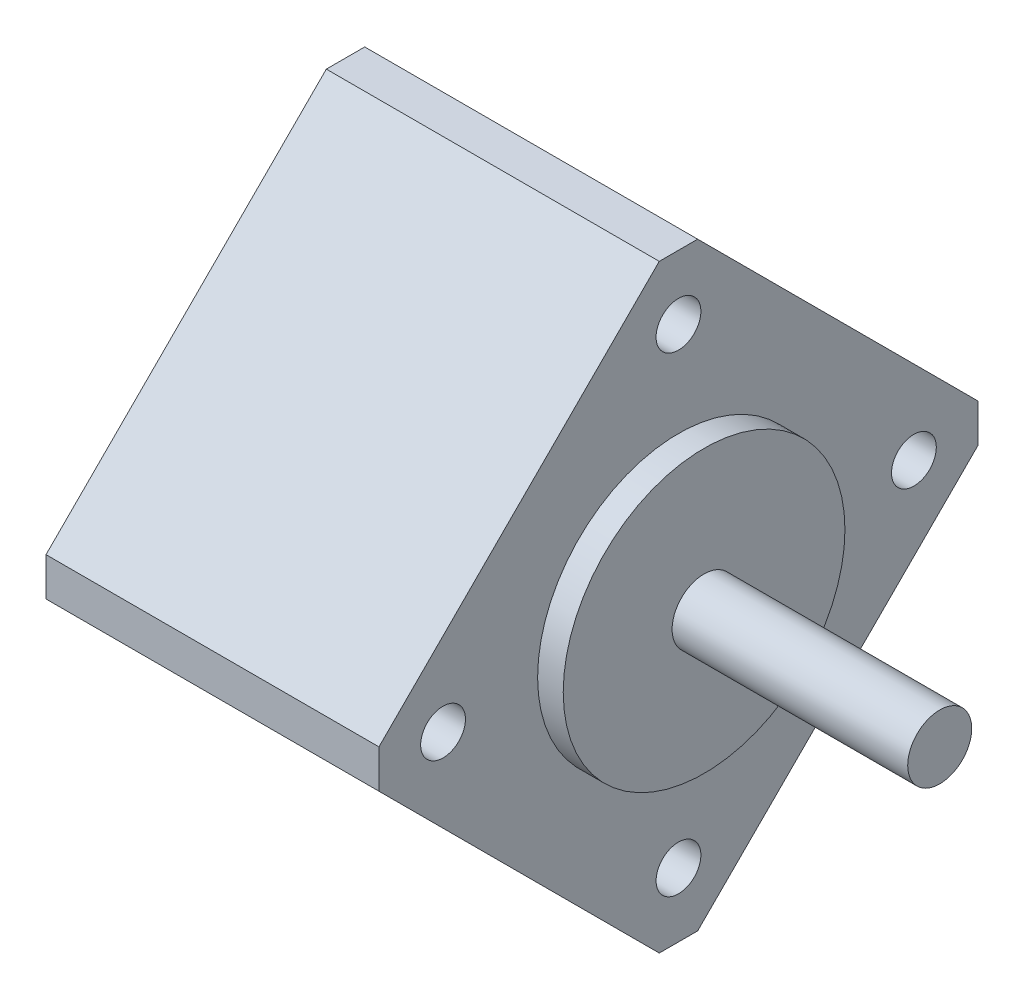
SolidWorks part; units mm, degrees
ref_plane "Front Plane" through (0, 0, 0) normal (0, 0, 1) x (1, 0, 0)
ref_plane "Top Plane" through (0, 0, 0) normal (0, 1, 0) x (1, 0, 0)
ref_plane "Right Plane" through (0, 0, 0) normal (1, 0, 0) x (0, 0, -1)
sketch "Sketch1" plane through (0, 0, 0) normal (0, 0, 1) x (1, 0, 0)
  line L0 (0, 0) -> (58.591, 0) construction
  line L2 (0, 0) -> (18.4, 0)
  line L3 (0, 0) -> (0, 2.5)
  line L4 (0, 2.5) -> (18.4, 2.5)
  line L5 (18.4, 0) -> (18.4, 2.5)
  line L6 (6.0094, 2.5) -> (6.0094, 6)
  line L11 (6.0094, 6) -> (9.9794, 6)
  line L16 (12.9794, 6) -> (12.9794, 3)
  line L17 (12.9794, 3) -> (13.6398, 3)
  line L18 (13.6398, 3) -> (13.6398, 2.5)
  line L19 (13.6398, 2.5) -> (6.0094, 2.5)
  line L22 (13.6398, 2.5) -> (16.1198, 2.5)
  line L23 (13.6398, 2.5) -> (13.6398, 4)
  line L24 (13.6398, 4) -> (16.1198, 4)
  line L25 (16.1198, 2.5) -> (16.1198, 4)
  line L27 (6.0094, 6) -> (9.9794, 6)
  line L28 (6.0094, 6) -> (6.0094, 9)
  line L29 (6.0094, 9) -> (9.9794, 9)
  line L30 (9.9794, 6) -> (9.9794, 9)
  line L31 (6.0094, 9) -> (6.0094, 8.25)
  line L32 (6.0094, 8.25) -> (5.0094, 8.25)
  line L33 (8.6609, 22.001) -> (8.6609, 12.476) construction
  line L34 (5.0094, 12.476) -> (12.3124, 12.476)
  line L35 (9.9794, 9) -> (12.3124, 9)
  line L36 (5.0094, 7.9375) -> (1.8344, 7.9375)
  line L37 (5.0094, 8.25) -> (5.0094, 12.476)
  line L38 (5.0094, 7.9375) -> (5.0094, 13.9365)
  line L39 (5.0094, 13.9365) -> (1.8344, 13.9365)
  line L40 (1.8344, 7.9375) -> (1.8344, 13.9365)
  line L41 (5.0094, 22.001) -> (12.3124, 22.001)
  line L42 (5.0094, 22.001) -> (5.0094, 30.1625)
  line L43 (5.0094, 30.1625) -> (12.3124, 30.1625)
  line L44 (12.3124, 22.001) -> (12.3124, 30.1625)
  line L49 (16.6398, 22.001) -> (16.6398, 7.5)
  line L51 (23.0198, 7.5) -> (23.0198, 6.5)
  line L54 (16.1198, 4) -> (13.6398, 4)
  line L56 (18.0398, 7.5) -> (23.0198, 7.5)
  line L57 (13.3124, 22.001) -> (16.6398, 22.001)
  line L58 (16.1198, 3.5) -> (20.0198, 3.5)
  line L59 (29.9098, 14) -> (26.9098, 11)
  line L60 (4.0094, 31.75) -> (18.0398, 31.75)
  line L61 (18.0398, 7.5) -> (23.0198, 7.5)
  line L62 (18.0398, 7.5) -> (18.0398, 12)
  line L63 (18.0398, 12) -> (23.0198, 12)
  line L64 (23.0198, 7.5) -> (23.0198, 12)
  line L65 (18.0398, 31.75) -> (18.0398, 12)
  line L66 (23.0198, 11) -> (26.9098, 11)
  line L67 (34.8098, 23) -> (31.3098, 19.5)
  line L68 (35.8098, 31) -> (38.7998, 33.99)
  line L69 (29.9098, 14) -> (29.9098, 15)
  line L70 (29.9098, 15) -> (22.9398, 15)
  line L71 (22.9398, 15) -> (21.0398, 15)
  line L72 (18.0398, 7.5) -> (16.6398, 7.5)
  line L73 (21.0398, 15) -> (21.0398, 43)
  line L74 (19.5798, 40) -> (9.6198, 40)
  line L75 (9.6198, 40) -> (4.0094, 40)
  line L76 (21.0398, 43) -> (19.5798, 43)
  line L77 (22.9398, 15) -> (29.9098, 15)
  line L78 (22.9398, 15) -> (22.9398, 21)
  line L79 (22.9398, 21) -> (29.9098, 21)
  line L80 (29.9098, 15) -> (29.9098, 21)
  line L81 (9.6198, 40) -> (19.5798, 40)
  line L82 (9.6198, 40) -> (9.6198, 50)
  line L83 (9.6198, 50) -> (19.5798, 50)
  line L84 (19.5798, 40) -> (19.5798, 50)
  line L85 (4.0094, 40) -> (4.0094, 31.75)
  line L86 (12.9794, 3) -> (12.9794, 2.5)
  line L87 (31.3098, 19.5) -> (29.9098, 19.5)
  line L88 (21.4694, 63.5) -> (21.4694, 51.308)
  line L89 (21.4694, 63.5) -> (25.9398, 63.5)
  line L90 (25.9398, 63.5) -> (25.9398, 25)
  line L91 (27.8398, 25) -> (25.9398, 25)
  line L92 (9.6198, 48) -> (8.1598, 48)
  line L93 (8.1598, 48) -> (8.1598, 53.476)
  line L94 (8.1598, 53.476) -> (19.5798, 53.476)
  line L95 (19.5798, 53.476) -> (19.5798, 50)
  line L96 (13.8698, 63.001) -> (13.8698, 53.476) construction
  line L97 (8.1598, 63.001) -> (19.5798, 63.001)
  line L98 (8.1598, 63.001) -> (8.1598, 68.2625)
  line L99 (8.1598, 68.2625) -> (19.5798, 68.2625)
  line L100 (19.5798, 63.001) -> (19.5798, 68.2625)
  line L101 (12.9794, 6) -> (11.9794, 6)
  line L102 (8.1598, 44.825) -> (4.9848, 44.825)
  line L103 (8.1598, 44.825) -> (8.1598, 54.9365)
  line L104 (8.1598, 54.9365) -> (4.9848, 54.9365)
  line L106 (9.9794, 6) -> (10.8794, 6)
  line L107 (27.8398, 25) -> (34.8098, 25)
  line L108 (34.8098, 25) -> (34.8098, 23)
  line L109 (0, 0) -> (-2, 0)
  line L110 (0, 0) -> (0, 11)
  line L111 (27.8398, 25) -> (34.8098, 25)
  line L112 (27.8398, 25) -> (27.8398, 32.5)
  line L113 (27.8398, 32.5) -> (34.8098, 32.5)
  line L114 (34.8098, 25) -> (34.8098, 32.5)
  line L115 (35.8098, 31) -> (34.8098, 31)
  line L116 (27.8398, 32.5) -> (27.8398, 64.5)
  line L117 (20.5373, 74.025) -> (6.2023, 74.025)
  line L118 (6.2023, 74.025) -> (6.2023, 76.2)
  line L119 (38.7998, 47.29) -> (30.8398, 55.25)
  line L120 (0, 11) -> (-2, 11)
  line L121 (38.7998, 43.815) -> (30.8623, 43.815)
  line L123 (-4.8152, 69.85) -> (1.5348, 76.2)
  line L124 (38.7998, 47.29) -> (38.7998, 33.99)
  line L125 (-2, 0) -> (-2, 11)
  line L126 (38.7998, 37.465) -> (30.8623, 37.465)
  line L127 (30.8623, 43.815) -> (30.8623, 37.465)
  line L128 (6.0094, 2.5) -> (6.0094, 0)
  line L129 (-0.0152, 63.5) -> (-0.0152, 30)
  line L132 (4.9848, 63.5) -> (-0.0152, 63.5)
  line L136 (-1.8152, 30) -> (-11.7752, 30)
  line L138 (-13.7752, 25.4) -> (-2, 25.4)
  line L139 (-2, 25.4) -> (-2, 11.5)
  line L140 (27.8398, 64.5) -> (20.5373, 64.5)
  line L141 (-1.8152, 30) -> (-11.7752, 30)
  line L142 (-1.8152, 30) -> (-1.8152, 39)
  line L143 (-1.8152, 39) -> (-11.7752, 39)
  line L144 (-11.7752, 30) -> (-11.7752, 39)
  line L145 (20.5373, 64.5) -> (20.5373, 74.025)
  line L146 (-12.7752, 37) -> (-12.7752, 47.29)
  line L147 (-12.7752, 37) -> (-11.7752, 37)
  line L148 (30.8398, 55.25) -> (30.8398, 76.2)
  line L149 (11.9794, 6) -> (11.9794, 5.45)
  line L154 (-2, 11.5) -> (0.5, 11.5)
  line L155 (4.9848, 60.6197) -> (24.0348, 60.6197)
  line L160 (4.9848, 60.6197) -> (4.9848, 55.8572)
  line L161 (4.9848, 55.8572) -> (24.0348, 55.8572)
  line L166 (24.0348, 60.6197) -> (24.0348, 55.8572)
  line L167 (4.9848, 60.6197) -> (24.0348, 55.8572) construction
  line L172 (4.9848, 55.8572) -> (24.0348, 60.6197) construction
  line L173 (24.0348, 62.2072) -> (25.9398, 62.2072)
  line L174 (11.9794, 5.45) -> (10.8794, 5.45)
  line L175 (10.8794, 6) -> (10.8794, 5.45)
  line L176 (24.0348, 62.2072) -> (24.0348, 54.2697)
  line L177 (24.0348, 54.2697) -> (25.9398, 54.2697)
  line L178 (25.9398, 62.2072) -> (25.9398, 54.2697)
  line L179 (24.0348, 62.2072) -> (25.9398, 54.2697) construction
  line L180 (24.0348, 54.2697) -> (25.9398, 62.2072) construction
  line L181 (3, 19.6197) -> (15.7, 19.6197)
  line L182 (3, 19.6197) -> (3, 14.8572)
  line L183 (3, 14.8572) -> (15.7, 14.8572)
  line L184 (15.7, 19.6197) -> (15.7, 14.8572)
  line L185 (3, 19.6197) -> (15.7, 14.8572) construction
  line L186 (3, 14.8572) -> (15.7, 19.6197) construction
  line L187 (15.7, 21.2072) -> (16.6398, 21.2072)
  line L188 (15.7, 21.2072) -> (15.7, 13.2697)
  line L189 (15.7, 13.2697) -> (16.6398, 13.2697)
  line L190 (16.6398, 21.2072) -> (16.6398, 13.2697)
  line L191 (15.7, 21.2072) -> (16.6398, 13.2697) construction
  line L192 (15.7, 13.2697) -> (16.6398, 21.2072) construction
  line L193 (0.5, 11.5) -> (0.5, 6.9375)
  line L194 (0.5, 6.9375) -> (1.8344, 6.9375)
  line L195 (23.0198, 6.5) -> (20.0198, 3.5)
  line L196 (4.9848, 63.5) -> (4.9848, 54.9365)
  line L197 (3, 43.825) -> (4.9848, 43.825)
  line L198 (1.8344, 6.9375) -> (1.8344, 7.9375)
  line L199 (6.0094, 0) -> (12.9794, 0)
  line L200 (12.9794, 0) -> (12.9794, 2.5)
  line L201 (18.0398, 31.75) -> (18.0398, 35.875)
  line L202 (18.0398, 35.875) -> (21.0398, 35.875)
  line L203 (30.8398, 76.2) -> (6.2023, 76.2)
  line L204 (2.7573, 69.85) -> (7.2023, 69.85) construction
  line L205 (7.2023, 67.4688) -> (26.2523, 67.4688)
  line L206 (7.2023, 74.025) -> (7.2023, 64.5)
  line L207 (7.2023, 64.5) -> (-1.8152, 64.5)
  line L208 (-1.8152, 64.5) -> (-1.8152, 39)
  line L209 (-12.7752, 47.29) -> (-4.8152, 55.25)
  line L210 (-4.8152, 55.25) -> (-4.8152, 69.85)
  line L211 (7.2023, 67.4688) -> (7.2023, 72.2312)
  line L212 (7.2023, 72.2312) -> (26.2523, 72.2313)
  line L213 (26.2523, 67.4688) -> (26.2523, 72.2313)
  line L214 (26.2523, 73.8187) -> (30.8398, 73.8187)
  line L215 (26.2523, 73.8187) -> (26.2523, 65.8813)
  line L216 (26.2523, 65.8813) -> (30.8398, 65.8813)
  line L217 (30.8398, 73.8187) -> (30.8398, 65.8813)
  line L218 (2.7573, 72.2313) -> (24.9823, 72.2313)
  line L219 (2.7573, 72.2313) -> (2.7573, 67.4687)
  line L220 (2.7573, 67.4687) -> (24.9823, 67.4687)
  line L221 (24.9823, 72.2313) -> (24.9823, 67.4687)
  line L222 (24.9823, 69.85) -> (20.5373, 69.85) construction
  line L223 (21.4694, 51.308) -> (22.9398, 51.308)
  line L224 (22.9398, 51.308) -> (22.9398, 21)
  line L225 (13.6398, 4) -> (13.6398, 12.2697)
  line L226 (13.6398, 12.2697) -> (13.3124, 12.2697)
  line L227 (13.3124, 12.2697) -> (13.3124, 22.001)
  line L228 (12.3124, 9) -> (12.3124, 12.476)
  line L229 (-1.8152, 30) -> (-0.0152, 30)
  line L230 (8.1598, 65.6317) -> (2.7573, 65.6317) construction
  line L231 (19.5798, 65.6317) -> (24.9823, 65.6317) construction
  line L232 (1.5348, 76.2) -> (6.2023, 76.2)
  line L233 (-11.7752, 30) -> (-13.7752, 30)
  line L234 (-13.7752, 30) -> (-13.7752, 25.4)
  line L235 (3, 13.9365) -> (3, 43.825)
  line L236 (4.9848, 54.9365) -> (4.9848, 44.825)
  line L237 (4.9848, 43.825) -> (4.9848, 44.825)
  circle A0 centre (26.8898, 25.95) radius 0.95
  circle A1 centre (21.9898, 15.95) radius 0.95
  circle A2 centre (17.3398, 8.2) radius 0.7
  circle A3 centre (10.4294, 6.45) radius 0.45
  circle A4 centre (-0.9152, 30.9) radius 0.9
  point P7 (24.9873, 58.2385)
  point P131 (16.1699, 17.2385)
  point P135 (14.5098, 58.2385)
  point P146 (9.35, 17.2385)
sketch "Sketch2" plane through (0, 0, 0) normal (0, 0, 1) x (1, 0, 0)
  line L0 (0, 0) -> (-2, 0) construction
  line L1 (0, 11) -> (-2, 11) construction
  line L2 (-2, 0) -> (-2, 11) construction
  line L3 (0, 0) -> (0, 11) construction
  line L4 (18.4, 0) -> (18.4, 2.5) construction
  line L5 (0, 0) -> (18.4, 0) construction
  line L6 (0, 2.5) -> (18.4, 2.5) construction
  line L7 (0, 0) -> (-2, 0)
  line L8 (0, 11) -> (-2, 11)
  line L9 (-2, 0) -> (-2, 11)
  line L10 (0, 0) -> (0, 11)
  line L11 (18.4, 0) -> (18.4, 2.5)
  line L12 (0, 0) -> (18.4, 0)
  line L13 (0, 2.5) -> (18.4, 2.5)
revolve "Revolve1" add sketch "Sketch2" angle 360 about L0 region at (-1, 5.5, 0) region at (9.2, 1.25, 0)
sketch "Sketch3" plane through (-2, 0, 0) normal (-1, 0, 0) x (0, 0, 1)
  line L0 (0, 23.3902) -> (1.5, 23.3902)
  line L1 (1.5, 23.3902) -> (23.3902, 1.5)
  line L2 (23.3902, 1.5) -> (23.3902, 0)
  line L3 (23.3902, -1.5) -> (1.5, -23.3902)
  line L4 (1.5, -23.3902) -> (0, -23.3902)
  line L5 (23.3902, 0) -> (23.3902, -1.5)
  line L6 (-1.5, -23.3902) -> (-23.3902, -1.5)
  line L7 (-23.3902, -1.5) -> (-23.3902, 0)
  line L8 (0, -23.3902) -> (-1.5, -23.3902)
  line L9 (-23.3902, 1.5) -> (-1.5, 23.3902)
  line L10 (-1.5, 23.3902) -> (0, 23.3902)
  line L11 (-23.3902, 0) -> (-23.3902, 1.5)
  circle A0 centre (0, 18.3848) radius 1.75
  circle A1 centre (18.3848, 0) radius 1.75
  circle A2 centre (0, -18.3848) radius 1.75
  circle A3 centre (-18.3848, 0) radius 1.75
  point P19 (0, 0)
  point P25 (0, 0)
  dimension "D5" = 3.5
  dimension "D2" = 35.2
  dimension "D3" = 3
  dimension "D6" = 26
  dimension "D1" = 4
  dimension "D4" = 4
extrude "Boss-Extrude1" add sketch "Sketch3" along normal blind 26
